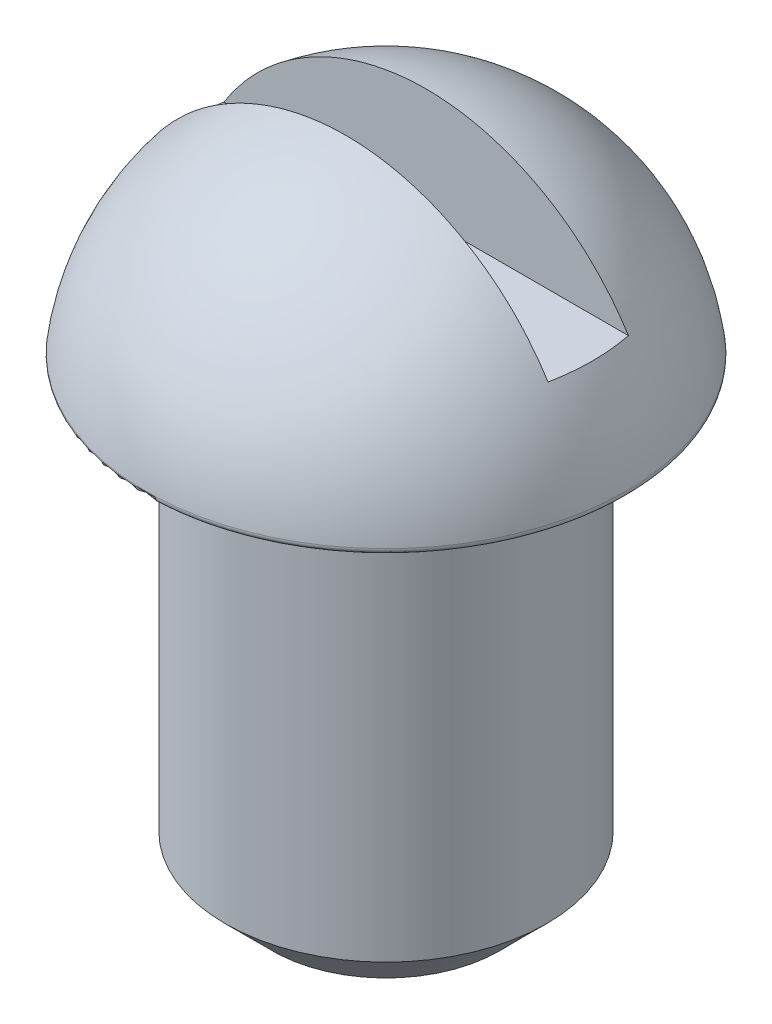
SolidWorks part; units mm, degrees
ref_plane "Спереди" through (0, 0, 0) normal (0, 0, 1) x (1, 0, 0)
ref_plane "Сверху" through (0, 0, 0) normal (0, 1, 0) x (1, 0, 0)
ref_plane "Справа" through (0, 0, 0) normal (1, 0, 0) x (0, 0, -1)
sketch "Эскиз1" plane through (0, 0, 0) normal (0, 0, 1) x (1, 0, 0)
  line L0 (0, 125.7632) -> (0, 0) construction
  line L1 (6, 86.2493) -> (9, 86.2493)
  line L2 (0, 94.2493) -> (0, 69.2493)
  line L3 (0, 94.2493) -> (1.5, 94.2493)
  line L4 (6, 86.2493) -> (6, 69.2493)
  line L6 (6, 69.2493) -> (0, 69.2493)
  arc A0 (1.5, 94.2493) -> (9, 86.2493) centre (-0.0484, 85.282) cw
  dimension "D1" = 1.5
  dimension "D2" = 8
  dimension "D3" = 25
  dimension "D4" = 9.1
  dimension "D5" = 6
  dimension "D6" = 9
revolve "Повернуть1" add sketch "Эскиз1" angle 360 about L0
ref_axis "Ось4" through (0, 1.4001, 0) along (0, -1, 0)
sketch "Эскиз13" plane through (0, 94.2493, 0) normal (0, 1, 0) x (-1, 0, 0)
  line L1 (9, -1.5) -> (-9, -1.5)
  line L2 (9, -1.5) -> (9, 1.5)
  line L3 (9, 1.5) -> (-9, 1.5)
  line L4 (-9, -1.5) -> (-9, 1.5)
  dimension "D1" = 9
  dimension "D2" = 18
  dimension "D3" = 1.5
  dimension "D4" = 3
extrude "Вырез-Вытянуть9" cut sketch "Эскиз13" against normal blind 4.2
fillet "Скругление1" radius 0.2 1 edges at (-9, 86.2493, 0)
chamfer "Фаска1" distance 1.75 angle 45 1 edges at (-6, 69.2493, 0)
